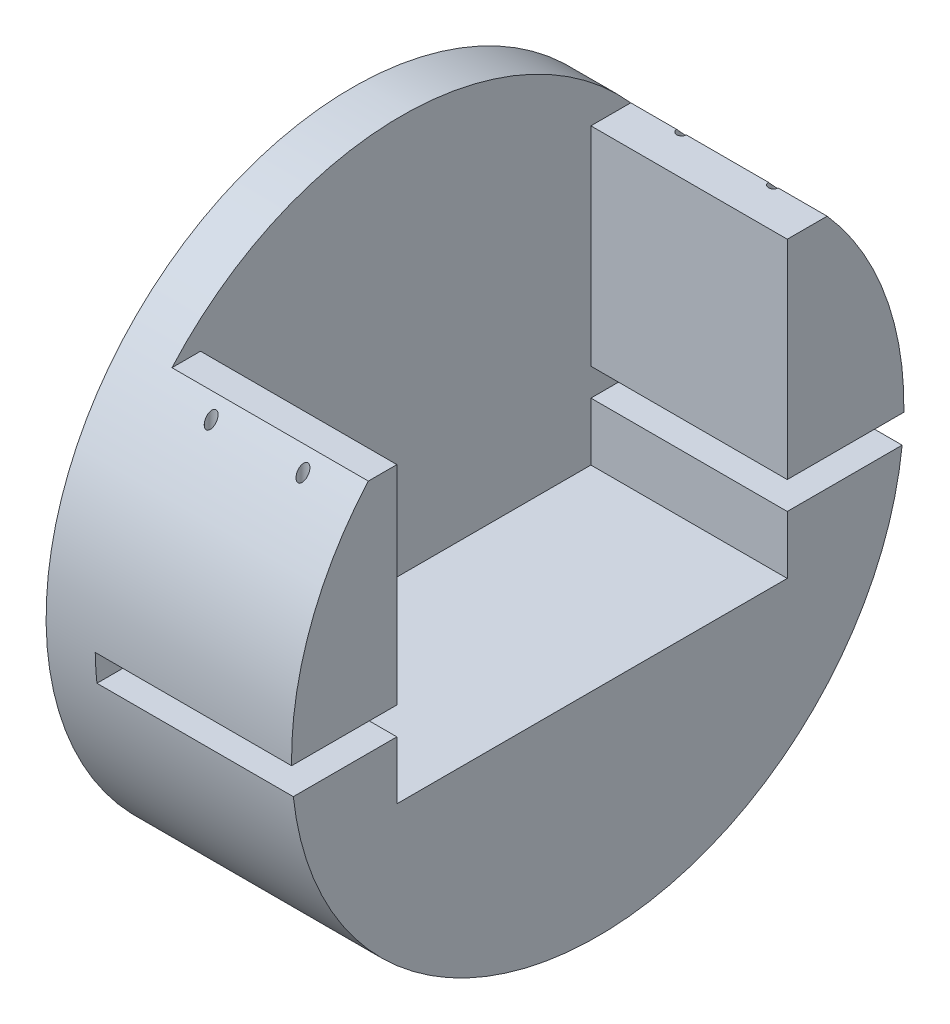
SolidWorks part; units mm, degrees
ref_plane "Front Plane" through (0, 0, 0) normal (0, 0, 1) x (1, 0, 0)
ref_plane "Top Plane" through (0, 0, 0) normal (0, 1, 0) x (1, 0, 0)
ref_plane "Right Plane" through (0, 0, 0) normal (1, 0, 0) x (0, 0, -1)
sketch "Sketch1" plane through (0, 0, 0) normal (1, 0, 0) x (0, 0, -1)
  circle A0 centre (0, 0) radius 31.6865
  dimension "D1" = 63.373
extrude "Boss-Extrude1" add sketch "Sketch1" along normal blind 25.4
sketch "Sketch3" plane through (25.4, 0, 0) normal (1, 0, 0) x (0, 0, -1)
  line L0 (-28.4027, 14.0471) -> (-27.7851, 20.9865)
  line L1 (-27.7851, 20.9865) -> (-20.7851, 20.9865)
  line L2 (-20.7851, 20.9865) -> (-20.7851, -9.415)
  line L3 (-20.7851, -9.415) -> (19.6149, -9.415)
  line L4 (19.6149, -9.415) -> (19.6149, -3.4135)
  line L5 (19.6149, -3.4135) -> (31.5021, -3.4135)
  line L6 (19.6149, 20.9865) -> (19.6149, 0.3865)
  line L7 (-20.7851, -0.556) -> (-31.6816, -0.556)
  line L8 (19.6149, 20.9865) -> (23.7403, 20.9865)
  line L10 (-20.7851, -3.4135) -> (-31.5021, -3.4135)
  line L11 (19.6149, 0.3865) -> (19.6149, -0.556)
  line L12 (19.6149, -0.556) -> (31.6816, -0.556)
  circle A0 centre (0, 0) radius 31.6865 construction
  circle A1 centre (0, 0) radius 33.5064
  circle M2 centre (0, 0) radius 31.6865
  dimension "D2" = 2.8575
extrude "Cut-Extrude1" cut sketch "Sketch3" against normal blind 20.32 contours L6 L8 L0 L1 L2 L3 L4 L5 M2 | L10 L2 M2 region at (25.4, -1.9808, 26.1994) region at (25.4, 9.8838, -0.0988)
sketch "Sketch5" plane through (0, 20.9865, 0) normal (0, 1, 0) x (1, 0, 0)
  circle A0 centre (10.33, -24.9326) radius 0.508
  circle A1 centre (19.83, -24.9326) radius 0.508
  circle A2 centre (10.33, 23.7623) radius 0.508
  circle A3 centre (19.83, 23.7623) radius 0.508
  dimension "D1" = 1.016
  dimension "D2" = 1.016
  dimension "D3" = 1.016
  dimension "D4" = 1.016
extrude "Cut-Extrude2" cut sketch "Sketch5" against normal blind 12.7
sketch "Sketch6" plane through (0, 0, 0) normal (-1, 0, 0) x (0, 0, 1)
  circle A0 centre (-1.5399, 19.9406) radius 0.508
  dimension "D1" = 1.016
extrude "Cut-Extrude3" cut sketch "Sketch6" against normal blind 3.556
